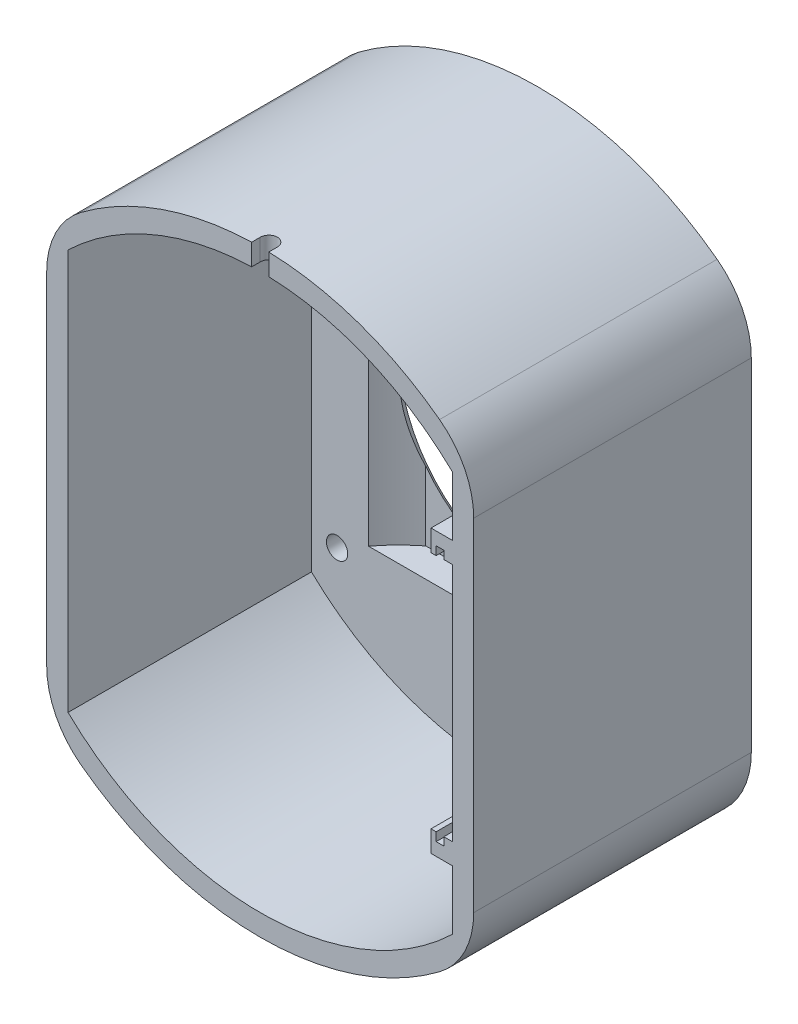
SolidWorks part; units mm, degrees
ref_plane "Спереди" through (0, 0, 0) normal (0, 0, 1) x (1, 0, 0)
ref_plane "Сверху" through (0, 0, 0) normal (0, 1, 0) x (1, 0, 0)
ref_plane "Справа" through (0, 0, 0) normal (1, 0, 0) x (0, 0, -1)
sketch "Эскиз1" plane through (0, 0, 0) normal (0, 0, 1) x (1, 0, 0)
  line L1 (45, -46.9042) -> (45, 46.9042)
  line L2 (0, 0) -> (0, -65) construction
  line L3 (50, -48.9898) -> (50, 48.9898)
  line L4 (-50, -48.9898) -> (-50, 48.9898)
  line L5 (-45, -46.9042) -> (-45, 46.9042)
  line L6 (-29.0575, -58.1435) -> (-29.0575, -34.0575)
  line L7 (-34.0575, -29.0575) -> (-45, -29.0575)
  line L8 (34.0575, -29.0575) -> (45, -29.0575)
  line L9 (29.0575, -58.1435) -> (29.0575, -34.0575)
  line L10 (34.0575, 29.0575) -> (45, 29.0575)
  line L11 (-39, -39) -> (39, 39) construction
  line L12 (-39, 39) -> (39, -39) construction
  line L13 (29.0575, 58.1435) -> (29.0575, 34.0575)
  line L14 (-34.0575, 29.0575) -> (-45, 29.0575)
  line L15 (-29.0575, 58.1435) -> (-29.0575, 34.0575)
  line L16 (-0.1, 27.5) -> (0.1, 27.5)
  line L17 (-27.5, -27.5) -> (27.5, -27.5) construction
  line L18 (-27.5, -27.5) -> (-27.5, 27.5) construction
  line L19 (-27.5, 27.5) -> (27.5, 27.5) construction
  line L20 (27.5, -27.5) -> (27.5, 27.5) construction
  line L21 (-27.5, -27.5) -> (27.5, 27.5) construction
  line L22 (-27.5, 27.5) -> (27.5, -27.5) construction
  line L23 (-27.5, 0.1) -> (-27.5, -0.1)
  line L24 (-0.1, -27.5) -> (0.1, -27.5)
  line L25 (27.5, 0.1) -> (27.5, -0.1)
  line L26 (-27.5, 27.5) -> (27.5, -27.5) construction
  line L27 (-27.5, -27.5) -> (27.5, 27.5) construction
  arc A0 (-45, -46.9042) -> (45, -46.9042) centre (0, 0) ccw
  arc A1 (50, 48.9898) -> (-50, 48.9898) centre (0, 0) ccw
  arc A2 (45, 46.9042) -> (-45, 46.9042) centre (0, 0) ccw
  circle A3 centre (0, 0) radius 65 construction
  circle A4 centre (0, 0) radius 70 construction
  arc A5 (-50, -48.9898) -> (50, -48.9898) centre (0, 0) ccw
  circle A6 centre (-39, -39) radius 2.5
  arc A7 (-29.0575, -34.0575) -> (-34.0575, -29.0575) centre (-34.0575, -34.0575) ccw
  circle A8 centre (39, -39) radius 2.5
  arc A9 (29.0575, -34.0575) -> (34.0575, -29.0575) centre (34.0575, -34.0575) cw
  circle A10 centre (39, 39) radius 2.5
  arc A11 (29.0575, 34.0575) -> (34.0575, 29.0575) centre (34.0575, 34.0575) ccw
  circle A12 centre (-39, 39) radius 2.5
  arc A13 (-29.0575, 34.0575) -> (-34.0575, 29.0575) centre (-34.0575, 34.0575) cw
  arc A14 (-27.5, -0.1) -> (-0.1, -27.5) centre (-0.1, -0.1) ccw
  arc A15 (-0.1, 27.5) -> (-27.5, 0.1) centre (-0.1, 0.1) ccw
  arc A16 (0.1, 27.5) -> (27.5, 0.1) centre (0.1, 0.1) cw
  arc A17 (0.1, -27.5) -> (27.5, -0.1) centre (0.1, -0.1) ccw
  point P4 (66.9413, 20.466)
  point P14 (65, 0)
  point P26 (-29.0575, -29.0575)
  dimension "D2" = 140
  dimension "D6" = 5
  dimension "D7" = 5
  dimension "D11" = 27.4
  dimension "D3" = 5
  dimension "D4" = 78
  dimension "D5" = 78
  dimension "D8" = 55
  dimension "D9" = 55
  dimension "D10" = 100
  dimension "D1" = 5
extrude "Extrude" add sketch "Эскиз1" along normal blind 65 contours L4 A5 L3 A1 A2 L1 A0 L5 region at (0, -68.2795, 0)
extrude "Boss-Extrude1" add sketch "Эскиз1<3>" along normal blind 8 contours L6 A7 L7 L5 A0 A6 | A9 L9 A0 L1 L8 A8 | L13 A11 L10 L1 A2 A10 | A15 A13 L15 A2 L5 L14 A12 | A15 A13 L14 L5 L7 A7 A14 L23 | A17 L24 A14 A7 L6 A0 L9 A9 | A17 A9 L8 L1 L10 A11 A16 L25 | L16 A16 A11 L13 A2 L15 A13 A15 region at (36.3642, -41.6012, 0) region at (39.5287, -27.4763, 0) region at (36.3642, 41.6012, 0) region at (-36.3642, -41.6012, 0) region at (-36.3642, 41.6012, 0)
sketch "Эскиз1<3>" plane through (0, 0, 0) normal (0, 0, 1) x (1, 0, 0) same geometry as "Эскиз1"
fillet "Fillet1" radius 20 4 edges at (50, -48.9898, 32.5) (-50, -48.9898, 32.5) (-50, 48.9898, 32.5) (50, 48.9898, 32.5)
chamfer "Chamfer3" distance 5 angle 45 8 edges at (27.5, 0, 0) (19.4747, 19.4747, 0) (19.4747, -19.4747, 0) (0, 27.5, 0) (0, -27.5, 0) (-19.4747, 19.4747, 0) (-19.4747, -19.4747, 0) (-27.5, 0, 0)
sketch "Sketch3" plane through (0, 0, 65) normal (0, 0, 1) x (1, 0, 0)
  line L0 (0, 0) -> (45, 0) construction
  line L1 (41.2, -28) -> (43, -28.1045)
  line L2 (45, -46.9042) -> (45, 46.9042) construction
  line L3 (45, 33) -> (40, 33)
  line L4 (40, 33) -> (40, 28)
  line L5 (40, 28) -> (41.2, 28)
  line L6 (41.2, 28) -> (41.2, 30)
  line L7 (41.2, 30) -> (43, 30)
  line L8 (43, 30) -> (43, 28.1045)
  line L9 (43, 28.1045) -> (45, 28.1045)
  line L10 (45, 28.1045) -> (45, 33)
  line L11 (43, -28.1045) -> (45, -28.1045)
  line L12 (43, -30) -> (43, -28.1045)
  line L13 (41.2, -30) -> (43, -30)
  line L14 (41.2, -28) -> (41.2, -30)
  line L15 (40, -28) -> (41.2, -28)
  line L16 (40, -33) -> (40, -28)
  line L17 (45, -33) -> (40, -33)
  line L18 (45, -28.1045) -> (45, -33)
  line L19 (41.2, 28) -> (43, 28.1045)
  point P7 (42.1, 30)
  dimension "D1" = 1.8
  dimension "D2" = 5
  dimension "D3" = 3
  dimension "D4" = 30
  dimension "D5" = 5
  dimension "D6" = 2
extrude "Boss-Extrude3" add sketch "Sketch3" against normal blind 10 contours L18 L12 L13 L14 L16 L17 | L16 L14 L15 | L10 L3 L4 L6 L7 L8 | L5 L6 L4 region at (42.5532, -30.779, 65) region at (42.5532, 30.779, 65)
extrude "Boss-Extrude4" add sketch "Sketch3<2>" along normal blind 10 from offset 45 contours L18 L12 L13 L14 L16 L17 | L16 L14 L15 | L10 L3 L4 L6 L7 L8 | L5 L6 L4 region at (42.5532, -30.779, 65) region at (42.5532, 30.779, 65) offset against normal yes
sketch "Sketch3<2>" plane through (0, 0, 65) normal (0, 0, 1) x (1, 0, 0) same geometry as "Sketch3"
sketch "Sketch5" plane through (0, 0, 0) normal (0, 1, 0) x (1, 0, 0)
  line L0 (0, 0) -> (0, -65) construction
  line L1 (-42, -65) -> (42, -65) construction
  line L2 (-2, -63) -> (-2, -65)
  line L3 (-2, -65) -> (2, -65)
  line L4 (2, -65) -> (2, -63)
  arc A0 (2, -63) -> (-2, -63) centre (0, -63) ccw
  circle A1 centre (5, -55) radius 1.1
  circle A2 centre (-5, -55) radius 1.1
  dimension "D1" = 4
  dimension "D2" = 2
  dimension "D3" = 2.2
  dimension "D4" = 5
  dimension "D5" = 10
extrude "Cut-Extrude2" cut sketch "Sketch5" along normal through all contours A0 L0 L3 L4 | L0 A0 L2 L3 region at (0.9335, 0, 63.1867) region at (-0.9335, 0, 63.1867)
extrude "Cut-Extrude3" cut sketch "Sketch5<4>" along normal blind 68 contours A2 | A1
sketch "Sketch5<4>" plane through (0, 0, 0) normal (0, 1, 0) x (1, 0, 0) same geometry as "Sketch5"
sketch "Sketch6" plane through (0, 0, 0) normal (0, 1, 0) x (1, 0, 0)
  line L0 (0, 0) -> (0, -65) construction
  line L1 (-45, -65) -> (45, -65) construction
  line L2 (-25, -1.25) -> (25, -1.25)
  line L3 (-45, -8) -> (45, -8) construction
  line L4 (31.6435, -8) -> (-0.1, -8)
  line L5 (-31.6435, -8) -> (0.1, -8)
  line L6 (42, 0) -> (-42, 0) construction
  arc A0 (25, -1.25) -> (31.6435, -8) centre (0, -32.5) cw
  arc A1 (-25, -1.25) -> (-31.6435, -8) centre (0, -32.5) ccw
  point P7 (0, -32.5)
  point P17 (0, -1.25)
  dimension "D1" = 25
  dimension "D2" = 1.25
extrude "Cut-Extrude4" cut sketch "Sketch6" against normal mid plane 70 contours L2 L0 L4 A0 | L0 L2 A1 L5 region at (14.3563, 0, 4.755) region at (-14.3563, 0, 4.755)
chamfer "Chamfer4" distance 2 angle 45 4 edges at (41.5, 39, 0) (-36.5, 39, 0) (-36.5, -39, 0) (41.5, -39, 0)
